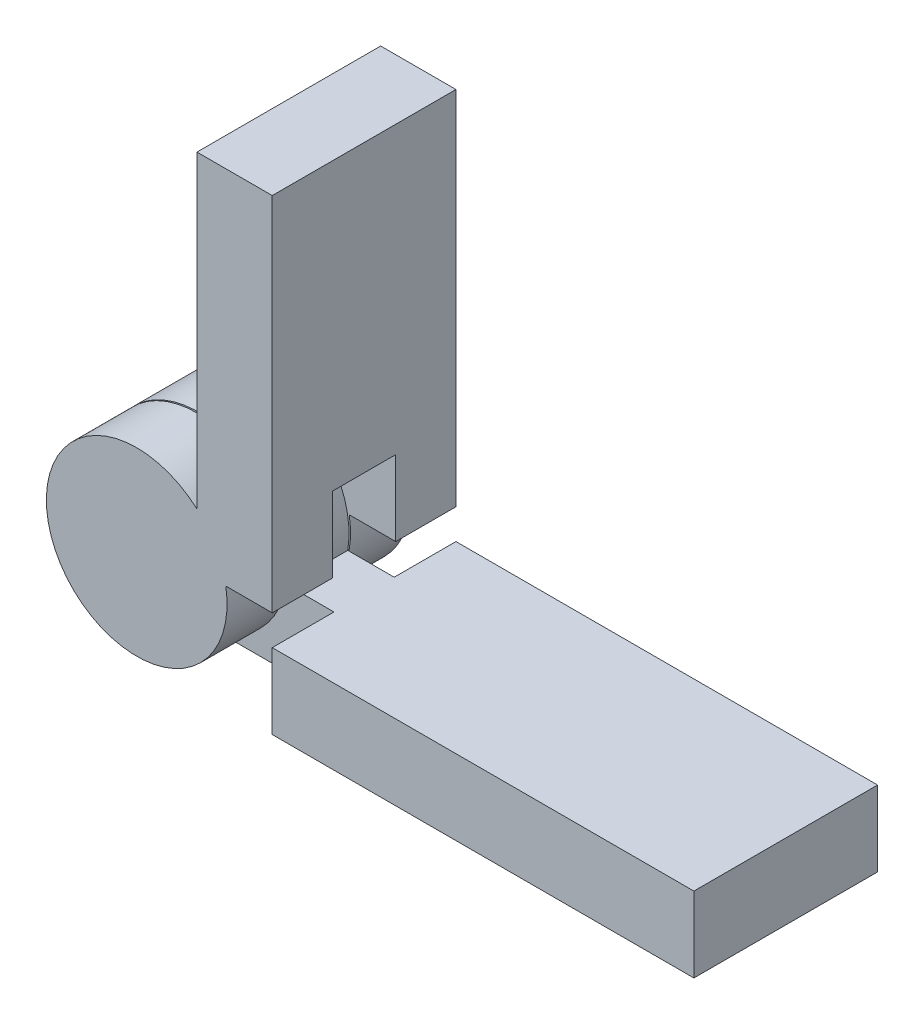
SolidWorks part; units mm, degrees
ref_plane "Front Plane" through (0, 0, 0) normal (0, 0, 1) x (1, 0, 0)
ref_plane "Top Plane" through (0, 0, 0) normal (0, 1, 0) x (1, 0, 0)
ref_plane "Right Plane" through (0, 0, 0) normal (1, 0, 0) x (0, 0, -1)
sketch "Sketch1" plane through (0, 0, 0) normal (0, 0, 1) x (1, 0, 0)
  circle A0 centre (-73.025, -41.275) radius 19.05
  circle A2 centre (-73.025, -41.275) radius 2.8702 construction
  dimension "D1" = 38.1
extrude "Boss-Extrude1" add sketch "Sketch1" along normal mid plane 12.7
sketch "Sketch2" plane through (0, 0, 6.35) normal (0, 0, 1) x (1, 0, 0)
  line L0 (-54.2414, -44.45) -> (44.45, -44.45)
  line L1 (44.45, -44.45) -> (44.45, -60.325)
  line L2 (44.45, -60.325) -> (-73.025, -60.325)
  line L3 (44.45, -44.45) -> (-44.45, -44.45) construction
  line L5 (44.45, 38.1) -> (44.45, -38.1) construction
  circle A0 centre (-73.025, -41.275) radius 19.05 construction
  arc A1 (-73.025, -60.325) -> (-54.2414, -44.45) centre (-73.025, -41.275) ccw
extrude "Boss-Extrude2" add sketch "Sketch2" against normal up to surface (12.7 mm away) up to face at (-53.975, -41.275, -6.35)
sketch "Sketch3" plane through (0, 0, 6.35) normal (0, 0, 1) x (1, 0, 0)
  circle A0 centre (-73.025, -41.275) radius 6.35
  dimension "D1" = 12.7
extrude "Cut-Extrude1" cut sketch "Sketch3" against normal through all
sketch "Sketch4" plane through (0, 0, 0) normal (0, 0, 1) x (1, 0, 0)
  circle A0 centre (-73.025, -41.275) radius 5.715
  dimension "D1" = 11.43
extrude "Boss-Extrude3" add sketch "Sketch4" against normal mid plane 13.335 separate body
sketch "Sketch5" plane through (0, 0, 6.6675) normal (0, 0, 1) x (1, 0, 0)
  circle A0 centre (-73.025, -41.275) radius 19.05
  arc A1 (-54.2414, -44.45) -> (-73.025, -60.325) centre (-73.025, -41.275) ccw construction
extrude "Boss-Extrude4" add sketch "Sketch5" along normal blind 12.7
sketch "Sketch6" plane through (0, 0, 19.3675) normal (0, 0, 1) x (1, 0, 0)
  line L0 (-44.45, -38.1) -> (-44.45, 38.1)
  line L1 (-44.45, 38.1) -> (-44.45, -38.1) construction
  line L2 (-44.45, 38.1) -> (-60.325, 38.1)
  line L3 (-60.325, 38.1) -> (-60.325, -27.076)
  line L4 (-44.45, -38.1) -> (-54.2414, -38.1)
  line L5 (-44.45, -38.1) -> (44.45, -38.1) construction
  circle A1 centre (-73.025, -41.275) radius 19.05 construction
  arc A2 (-60.325, -27.076) -> (-54.2414, -38.1) centre (-73.025, -41.275) cw
  dimension "D1" = 15.875
extrude "Boss-Extrude5" add sketch "Sketch6" against normal up to surface (12.7 mm away) up to face at (-67.31, -41.275, 6.6675)
ref_plane "Silo Hinge Mid Plane" through (0, 0, 0) normal (0, 0, 1) x (1, 0, 0)
mirror "Mirror1" about plane through (0, 0, 0) normal (0, 0, 1) of "Boss-Extrude5", "Boss-Extrude4"
sketch "Sketch7" plane through (0, 0, 6.6675) normal (0, 0, -1) x (-1, 0, 0)
  line L0 (60.325, -27.076) -> (60.325, 38.1) construction
  line L1 (44.45, 38.1) -> (60.325, 38.1)
  line L2 (44.45, 38.1) -> (44.45, -22.225)
  line L3 (44.45, -22.225) -> (60.325, -22.225)
  line L4 (60.325, 38.1) -> (60.325, -22.225)
  line L5 (98.7602, -22.225) -> (64.3668, -22.225) construction
  arc A0 (54.2414, -38.1) -> (60.325, -27.076) centre (73.025, -41.275) ccw construction
extrude "Boss-Extrude6" add sketch "Sketch7" along normal up to surface (13.335 mm away) up to face at (-78.74, -41.275, -6.6675)
sketch "Sketch8" plane through (0, 0, 6.35) normal (0, 0, 1) x (1, 0, 0)
  line L0 (44.45, -44.45) -> (-54.2414, -44.45) construction
  line L1 (44.45, -60.325) -> (-44.45, -60.325)
  line L2 (44.45, -60.325) -> (44.45, -44.45)
  line L3 (44.45, -44.45) -> (-44.45, -44.45)
  line L4 (-44.45, -60.325) -> (-44.45, -44.45)
extrude "Boss-Extrude7" add sketch "Sketch8" along normal up to surface (13.0175 mm away) and the other way up to surface (25.7175 mm away) up to face at (-59.2424, -8.9934, 19.3675) other way up to face at (-59.2424, -8.9934, -19.3675)
